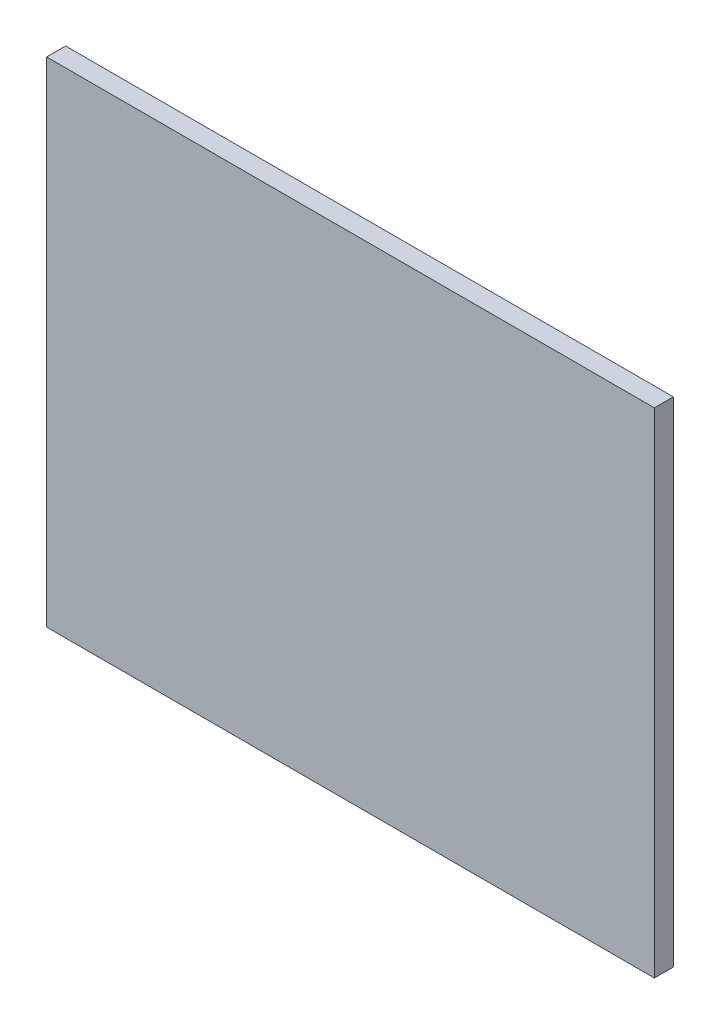
SolidWorks part; units mm, degrees
ref_plane "Front Plane" through (0, 0, 0) normal (0, 0, 1) x (1, 0, 0)
ref_plane "Top Plane" through (0, 0, 0) normal (0, 1, 0) x (1, 0, 0)
ref_plane "Right Plane" through (0, 0, 0) normal (1, 0, 0) x (0, 0, -1)
sketch "Sketch1" plane through (0, 0, 0) normal (0, 0, 1) x (1, 0, 0)
  line L1 (0, 0) -> (203.2, 0)
  line L2 (0, 0) -> (0, 165.1)
  line L3 (0, 165.1) -> (203.2, 165.1)
  line L4 (203.2, 0) -> (203.2, 165.1)
  dimension "D1" = 203.2
  dimension "D2" = 165.1
extrude "Boss-Extrude1" add sketch "Sketch1" along normal blind 6.35
